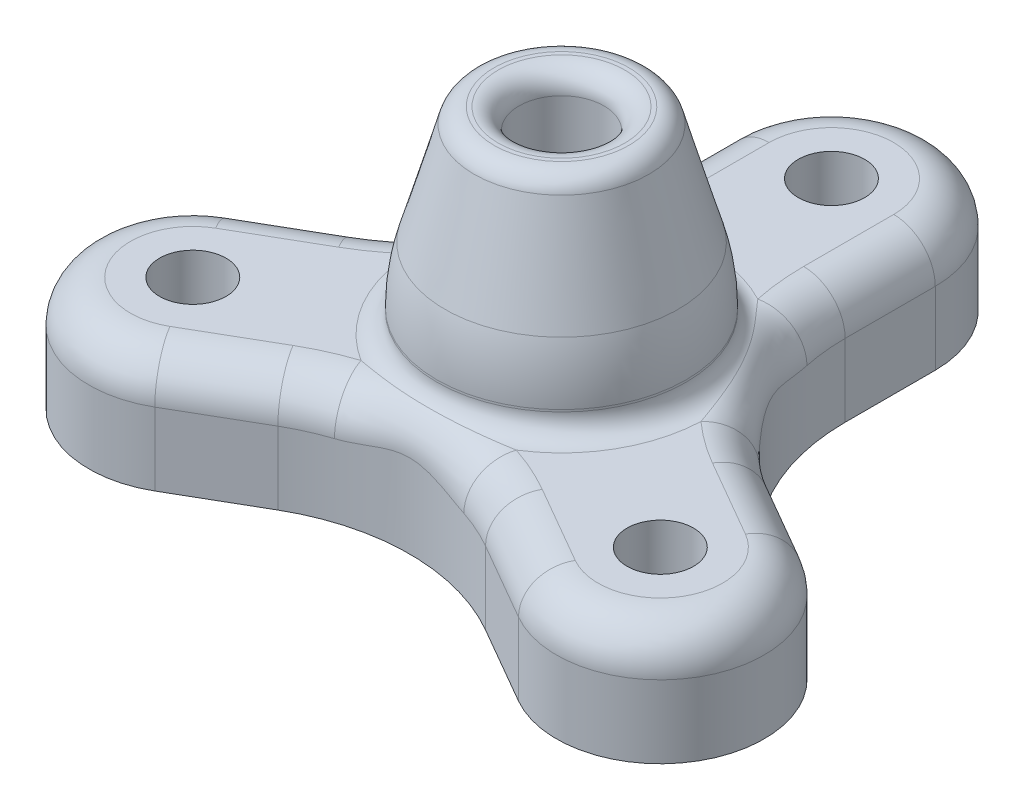
SolidWorks part; units mm, degrees
ref_plane "Front Plane" through (0, 0, 0) normal (0, 0, 1) x (1, 0, 0)
ref_plane "Top Plane" through (0, 0, 0) normal (0, 1, 0) x (1, 0, 0)
ref_plane "Right Plane" through (0, 0, 0) normal (1, 0, 0) x (0, 0, -1)
sketch "Sketch1" plane through (0, 0, 0) normal (0, 1, 0) x (1, 0, 0)
  line L0 (0, 0) -> (0, 18.595) construction
  line L1 (0, 0) -> (-14.8098, -8.5504) construction
  line L2 (0, 0) -> (16.4931, -9.5223) construction
  line L3 (-5, 13) -> (-5, 8.6603)
  line L4 (0, 4.0992) -> (-3.55, 2.0496)
  line L5 (-3.55, 2.0496) -> (-3.55, -2.0496)
  line L6 (-3.55, -2.0496) -> (0, -4.0992)
  line L7 (0, -4.0992) -> (3.55, -2.0496)
  line L8 (3.55, -2.0496) -> (3.55, 2.0496)
  line L9 (3.55, 2.0496) -> (0, 4.0992)
  line L10 (-13.7583, -2.1699) -> (-10, 0)
  line L11 (5, 13) -> (5, 8.6603)
  line L12 (10, 0) -> (13.7583, -2.1699)
  line L13 (-8.7583, -10.8301) -> (-5, -8.6603)
  line L14 (5, -8.6603) -> (8.7583, -10.8301)
  circle A0 centre (0, 0) radius 13 construction
  circle A1 centre (0, 13) radius 1.6
  circle A2 centre (-11.2583, -6.5) radius 1.6
  circle A3 centre (11.2583, -6.5) radius 1.6
  circle A4 centre (0, 0) radius 3.55 construction
  arc A5 (5, 13) -> (-5, 13) centre (0, 13) ccw
  arc A6 (-13.7583, -2.1699) -> (-8.7583, -10.8301) centre (-11.2583, -6.5) ccw
  arc A7 (8.7583, -10.8301) -> (13.7583, -2.1699) centre (11.2583, -6.5) ccw
  arc A8 (-5, -8.6603) -> (5, -8.6603) centre (0, -17.3205) cw
  arc A9 (5, 8.6603) -> (10, 0) centre (15, 8.6603) ccw
  arc A10 (-5, 8.6603) -> (-10, 0) centre (-15, 8.6603) cw
  dimension "D1" = 26
  dimension "D4" = 3.2
  dimension "D5" = 7.1
  dimension "D6" = 10
  dimension "D7" = 10
  dimension "D2" = 120
  dimension "D3" = 120
extrude "Boss-Extrude1" add sketch "Sketch1" along normal blind 5.5
sketch "Sketch2" plane through (0, 5.5, 0) normal (0, 1, 0) x (1, 0, 0)
  line L1 (0, 4.0992) -> (-3.55, 2.0496)
  line L2 (-3.55, 2.0496) -> (-3.55, -2.0496)
  line L3 (-3.55, -2.0496) -> (0, -4.0992)
  line L4 (0, -4.0992) -> (3.55, -2.0496)
  line L5 (3.55, -2.0496) -> (3.55, 2.0496)
  line L6 (3.55, 2.0496) -> (0, 4.0992)
  circle A0 centre (0, 0) radius 3.55 construction
  circle A1 centre (0, 0) radius 6
  dimension "D1" = 12
extrude "Boss-Extrude2" add sketch "Sketch2" along normal blind 2.5
sketch "Sketch3" plane through (0, 8, 0) normal (0, 1, 0) x (1, 0, 0)
  circle A0 centre (0, 0) radius 2.05
  circle A1 centre (0, 0) radius 4
  dimension "D1" = 4.1
  dimension "D2" = 8
extrude "Boss-Extrude4" add sketch "Sketch3" along normal blind 7
sketch "Sketch7" plane through (0, 8, 0) normal (0, -1, 0) x (1, 0, 0)
  circle A0 centre (0, 0) radius 2.05
  circle A1 centre (0, 0) radius 4.0992
  circle A2 centre (0, 0) radius 2.05 construction
extrude "Boss-Extrude6" add sketch "Sketch7" along normal offset from surface (4.5 mm away) 3.5 up to face at (11.2583, 0, 8.1)
ref_axis "Axis1" through (0, 15, 0) along (0, -1, 0)
sketch "Sketch4" plane through (0, 0, 0) normal (0, 0, 1) x (1, 0, 0)
  line L0 (-6, 8) -> (-4, 15)
  line L1 (-4, 15) -> (-4, 8)
  line L2 (-4, 8) -> (-6, 8)
revolve "Revolve1" add sketch "Sketch4" angle 360 about axis through (0, 15, 0) along (0, -1, 0)
sketch "Sketch5" plane through (0, 3.5, 0) normal (0, -1, 0) x (1, 0, 0)
  circle A0 centre (0, 0) radius 2.05
  circle A2 centre (0, 0) radius 2.05 construction
extrude "Boss-Extrude5" add sketch "Sketch5" against normal blind 0.2
fillet "Fillet1" radius 1 3 edges at (0, 5.5, 6) (0, 15, 2.05) (0, 15, 4)
fillet "Fillet2" radius 2 12 edges at (-6.8792, 5.5, 9.7452) (-15.5885, 5.5, 9) (-11.8792, 5.5, 1.0849) (-6.3397, 5.5, -3.6603) (-5, 5.5, -10.8301) (0, 5.5, -18) (5, 5.5, -10.8301) (6.3397, 5.5, -3.6603) (11.8792, 5.5, 1.0849) (15.5885, 5.5, 9) (6.8792, 5.5, 9.7452) (0, 5.5, 7.3205)
fillet "Fillet3" radius 10 1 edges at (0, 8, 6)
